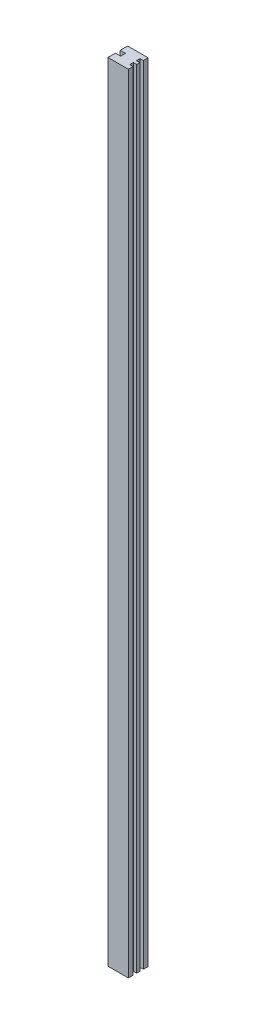
SolidWorks part; units mm, degrees
ref_plane "Спереди" through (0, 0, 0) normal (0, 0, 1) x (1, 0, 0)
ref_plane "Сверху" through (0, 0, 0) normal (0, 1, 0) x (1, 0, 0)
ref_plane "Справа" through (0, 0, 0) normal (1, 0, 0) x (0, 0, -1)
sketch "Эскиз1" plane through (0, 0, 0) normal (0, 1, 0) x (1, 0, 0)
  line L0 (0, 3.6577) -> (0, -3.6577)
  line L1 (0, -3.6577) -> (-7.957, -3.6577)
  line L2 (-7.957, -3.6577) -> (-7.957, -15.1002)
  line L3 (-7.957, -15.1002) -> (23.1476, -15.1002)
  line L4 (23.1476, -15.1002) -> (23.1476, -7.8666)
  line L5 (23.1476, -7.8666) -> (18.0908, -7.8666)
  line L6 (18.0908, -7.8666) -> (18.0908, -2.372)
  line L7 (-18.9883, 0) -> (46.2952, 0) construction
  line L8 (18.0908, -2.372) -> (23.1476, -2.372)
  line L9 (23.1476, -2.372) -> (23.1476, 2.372)
  line L10 (18.0908, 2.372) -> (23.1476, 2.372)
  line L11 (18.0908, 7.8666) -> (18.0908, 2.372)
  line L12 (23.1476, 7.8666) -> (18.0908, 7.8666)
  line L13 (23.1476, 15.1002) -> (23.1476, 7.8666)
  line L14 (-7.957, 15.1002) -> (23.1476, 15.1002)
  line L15 (-7.957, 3.6577) -> (-7.957, 15.1002)
  line L16 (0, 3.6577) -> (-7.957, 3.6577)
  point P14 (23.1476, 0)
  point P21 (0, 0)
extrude "Бобышка-Вытянуть1" add sketch "Эскиз1" along normal blind 1200
